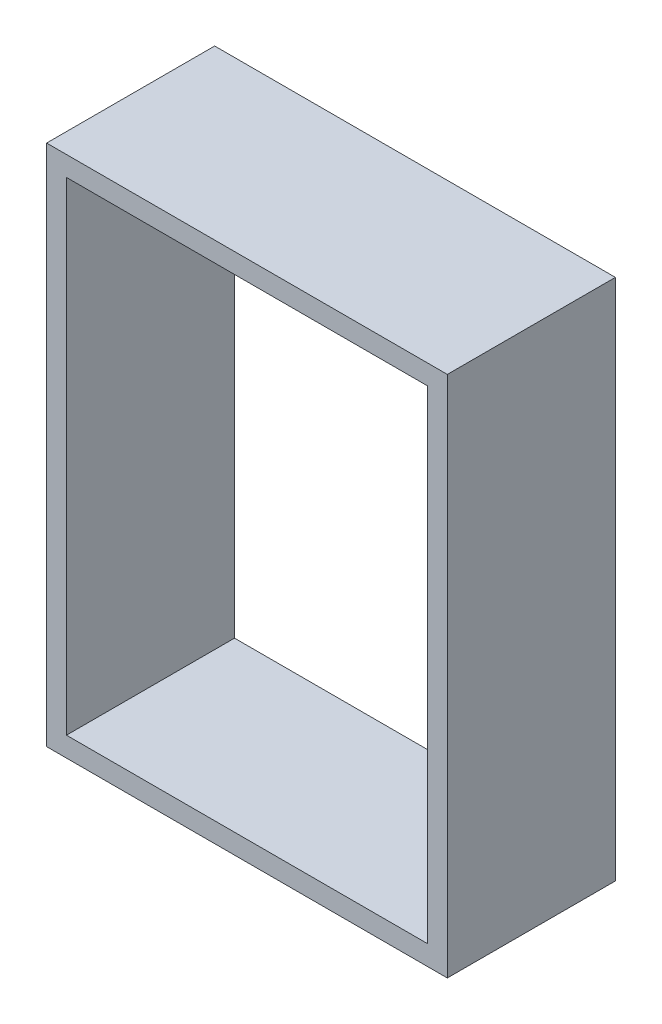
SolidWorks part; units mm, degrees
ref_plane "Front Plane" through (0, 0, 0) normal (0, 0, 1) x (1, 0, 0)
ref_plane "Top Plane" through (0, 0, 0) normal (0, 1, 0) x (1, 0, 0)
ref_plane "Right Plane" through (0, 0, 0) normal (1, 0, 0) x (0, 0, -1)
sketch "Strap Sketch" plane through (0, 0, 0) normal (0, 0, 1) x (1, 0, 0)
  line L0 (-25.55, 5.25) -> (4.73, 5.25)
  line L1 (4.73, 5.25) -> (4.73, 44.75)
  line L2 (4.73, 44.75) -> (-25.55, 44.75)
  line L3 (-25.55, 44.75) -> (-25.55, 5.25)
  line L4 (-24.05, 6.75) -> (3.23, 6.75)
  line L5 (3.23, 6.75) -> (3.23, 43.25)
  line L6 (3.23, 43.25) -> (-24.05, 43.25)
  line L7 (-24.05, 43.25) -> (-24.05, 6.75)
extrude "Strap" add sketch "Strap Sketch" along normal mid plane 12.7
ref_axis "Engine Axis" through (6.244, 0, 0) along (-1, 0, 0)
